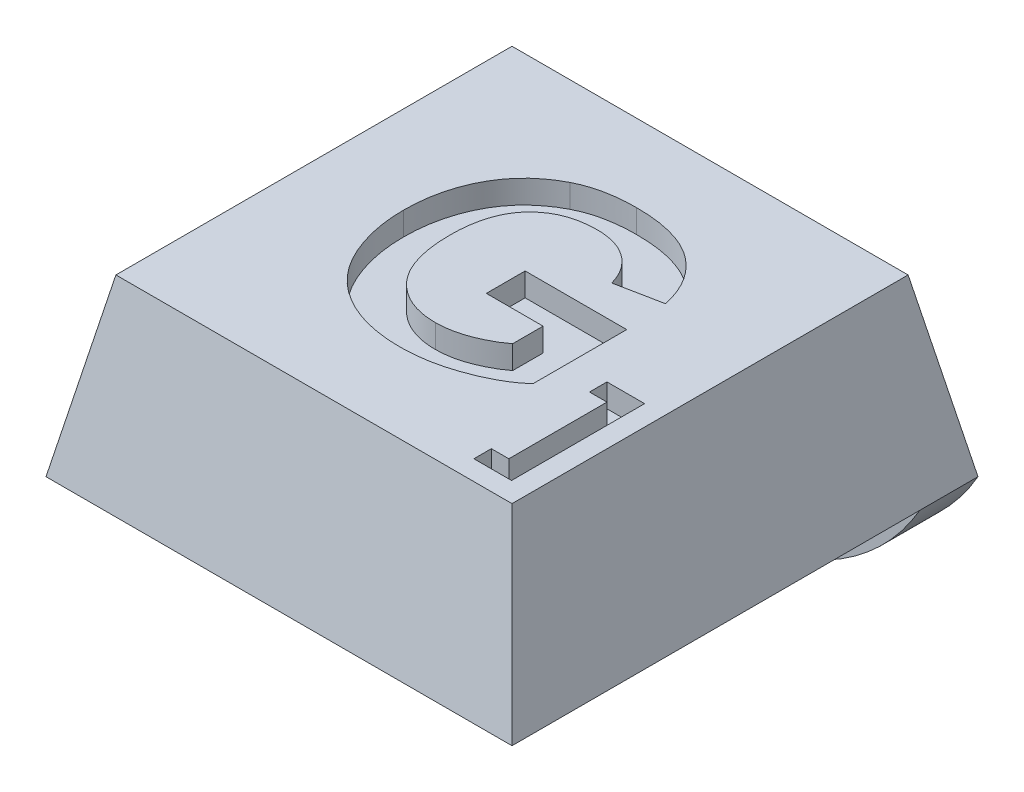
SolidWorks part; units mm, degrees
ref_plane "Front Plane" through (0, 0, 0) normal (0, 0, 1) x (1, 0, 0)
ref_plane "Top Plane" through (0, 0, 0) normal (0, 1, 0) x (1, 0, 0)
ref_plane "Right Plane" through (0, 0, 0) normal (1, 0, 0) x (0, 0, -1)
sketch "Sketch1" plane through (0, 0, 0) normal (0, 1, 0) x (1, 0, 0)
  line L1 (0, 0) -> (8, 0)
  line L2 (0, 0) -> (0, 8)
  line L3 (0, 8) -> (8, 8)
  line L4 (8, 0) -> (8, 8)
  dimension "D1" = 8
  dimension "D2" = 8
extrude "Boss-Extrude1" add sketch "Sketch1" along normal blind 3
sketch "Sketch2" plane through (0, 0, 0) normal (0, 0, 1) x (1, 0, 0)
  line L0 (0, 0) -> (0.6, 3)
  line L1 (0, 3) -> (8, 3) construction
  line L2 (0.6, 3) -> (0, 3)
  line L3 (0, 3) -> (0, 0)
  line L4 (8, 0) -> (7.4, 3)
  line L5 (7.4, 3) -> (8, 3)
  line L6 (8, 3) -> (8, 0)
  dimension "D1" = 0.6
  dimension "D2" = 0.6
extrude "Cut-Extrude1" cut sketch "Sketch2" against normal through all both and the other way through all
sketch "Sketch3" plane through (0, 0, 0) normal (1, 0, 0) x (0, 0, -1)
  line L0 (0, 0) -> (0.6, 3)
  line L1 (8, 3) -> (0, 3) construction
  line L2 (0.6, 3) -> (0, 3)
  line L3 (0, 3) -> (0, 0)
  line L4 (8, 3) -> (7.4, 3)
  line L5 (7.4, 3) -> (8, 0)
  line L6 (8, 3) -> (8, 0)
  dimension "D1" = 0.6
  dimension "D2" = 0.6
extrude "Cut-Extrude2" cut sketch "Sketch3" along normal blind 11
sketch "Sketch4" plane through (0, 0, 0) normal (0, -1, 0) x (1, 0, 0)
  line L0 (8, 0) -> (8, -8) construction
  line L3 (0, 0) -> (8, 0) construction
  circle A0 centre (4, -3.75) radius 1.75
  dimension "D1" = 3.5
  dimension "D2" = 4
  dimension "D3" = 3.75
extrude "Cut-Extrude3" cut sketch "Sketch4" against normal blind 0.4
sketch "Sketch5" plane through (0, 0, 0) normal (0, -1, 0) x (1, 0, 0)
  line L0 (8, 0) -> (8, -8) construction
  line L1 (0, -8) -> (8, -8)
  line L2 (0, -8) -> (0, -7)
  line L3 (0, -7) -> (8, -7)
  line L4 (8, -8) -> (8, -7)
  dimension "D1" = 1
extrude "Boss-Extrude2" add sketch "Sketch5" along normal blind 2
fillet "Fillet1" radius 4 2 edges at (8, -2, -7.5) (0, -2, -7.5)
sketch "Sketch6" plane through (0, 3, 0) normal (0, 1, 0) x (1, 0, 0)
  text T0 "G" font "Arial" height 4
extrude "Cut-Extrude4" cut sketch "Sketch6" against normal blind 0.4
sketch "Sketch7" plane through (0, 3, 0) normal (0, 1, 0) x (1, 0, 0)
  text T0 "]" font "Arial" height 1.8
extrude "Cut-Extrude5" cut sketch "Sketch7" against normal blind 0.4
